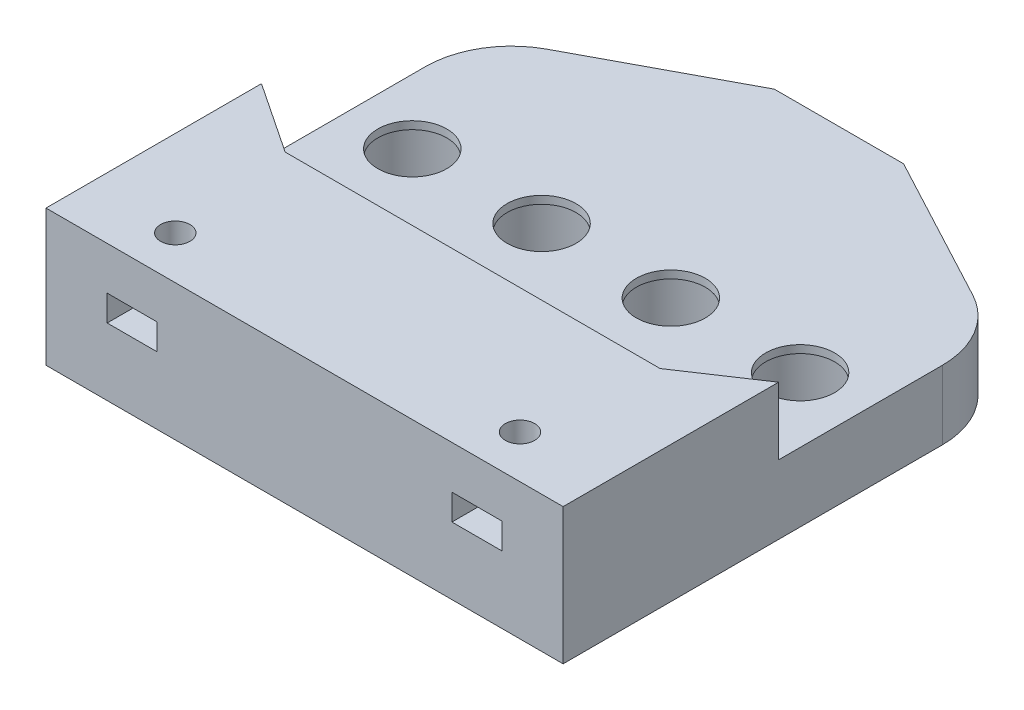
SolidWorks part; units mm, degrees
ref_plane "Front Plane" through (0, 0, 0) normal (0, 0, 1) x (1, 0, 0)
ref_plane "Top Plane" through (0, 0, 0) normal (0, 1, 0) x (1, 0, 0)
ref_plane "Right Plane" through (0, 0, 0) normal (1, 0, 0) x (0, 0, -1)
sketch "Sketch2" plane through (0, 0, 0) normal (0, 1, 0) x (1, 0, 0)
  line L0 (0, 0) -> (0, 35)
  line L1 (0, 35) -> (22.5, 47)
  line L2 (22.5, 47) -> (37.5, 47)
  line L3 (37.5, 47) -> (60, 35)
  line L4 (60, 35) -> (60, 0)
  line L5 (60, 0) -> (0, 0)
  line L6 (22.5, 20) -> (37.5, 20) construction
  line L7 (30, 47) -> (30, 0) construction
  circle A0 centre (7.5, 20) radius 4
  circle A1 centre (22.5, 20) radius 4
  circle A2 centre (37.5, 20) radius 4
  circle A3 centre (52.5, 20) radius 4
  point P17 (30, 20)
  dimension "D5" = 8
  dimension "D7" = 15
  dimension "D8" = 15
  dimension "D9" = 15
  dimension "D6" = 20
  dimension "D1" = 60
  dimension "D2" = 35
  dimension "D3" = 15
  dimension "D4" = 12
extrude "Boss-Extrude1" add sketch "Sketch2" along normal blind 8
sketch "Sketch3" plane through (0, 8, 0) normal (0, 1, 0) x (1, 0, 0)
  line L0 (0, 0) -> (0, 10)
  line L1 (0, 35) -> (0, 0) construction
  line L2 (0, 10) -> (15, 0)
  line L3 (0, 0) -> (60, 0) construction
  line L4 (15, 0) -> (0, 0)
  line L5 (60, 0) -> (60, 10)
  line L6 (60, 0) -> (60, 35) construction
  line L7 (60, 10) -> (45, 0)
  line L8 (45, 0) -> (60, 0)
  line L9 (51.75, 4.5) -> (8.25, 4.5)
  line M8 (0, 0) -> (60, 0)
  line M9 (60, 0) -> (60, 35)
  line M13 (0, 35) -> (0, 0)
  dimension "D1" = 15
  dimension "D2" = 10
  dimension "D3" = 4.5
extrude "Boss-Extrude2" add sketch "Sketch3" along normal blind 7.8 contours L2 M13 M8 | L7 L9 L2 M8 | L7 M9 M8 region at (5, 8, -3.3333) region at (30, 8, -2.3878) region at (55, 8, -3.3333)
sketch "Sketch5" plane through (0, 0, 0) normal (0, 1, 0) x (1, 0, 0)
  circle A0 centre (7.5, 20) radius 6.55
  circle A1 centre (22.5, 20) radius 6.55
  circle A2 centre (37.5, 20) radius 6.55
  circle A3 centre (52.5, 20) radius 6.55
  dimension "D1" = 13.1
extrude "Cut-Extrude2" cut sketch "Sketch5" along normal blind 7.1
fillet "Fillet1" radius 10 2 edges at (0, 4, -35) (60, 4, -35)
sketch "Sketch7" plane through (0, 0, 0) normal (0, 0, 1) x (1, 0, 0)
  line L1 (0, 15.8) -> (60, 15.8)
  line L2 (0, 15.8) -> (0, 0)
  line L3 (0, 0) -> (60, 0)
  line L4 (60, 15.8) -> (60, 0)
extrude "Boss-Extrude3" add sketch "Sketch7" along normal blind 15
sketch "Sketch8" plane through (0, 15.8, 0) normal (0, 1, 0) x (1, 0, 0)
  line L0 (60, -15) -> (0, -15) construction
  line L1 (0, 10) -> (0, -15) construction
  line L2 (30, 47) -> (30, -15) construction
  line L3 (37.5, 47) -> (22.5, 47) construction
  circle A0 centre (10, -10) radius 1.7
  circle A1 centre (50, -10) radius 1.7
  dimension "D1" = 3.4
  dimension "D2" = 5
  dimension "D3" = 10
extrude "Cut-Extrude3" cut sketch "Sketch8" against normal blind 10
sketch "Sketch9" plane through (0, 15.8, 0) normal (0, 1, 0) x (1, 0, 0)
  line L0 (30, -15) -> (30, 47) construction
  line L1 (52.9, -8.3257) -> (50, -6.6514)
  line L2 (50, -6.6514) -> (47.1, -8.3257)
  line L3 (47.1, -8.3257) -> (47.1, -11.6743)
  line L4 (47.1, -11.6743) -> (50, -13.3486)
  line L5 (50, -13.3486) -> (52.9, -11.6743)
  line L6 (52.9, -11.6743) -> (52.9, -8.3257)
  line L7 (60, -15) -> (0, -15) construction
  line L8 (37.5, 47) -> (22.5, 47) construction
  line L9 (52.9, -11.6743) -> (52.9, -15)
  line L10 (52.9, -15) -> (47.1, -15)
  line L11 (47.1, -15) -> (47.1, -11.6743)
  line L12 (12.9, -15) -> (12.9, -11.6743)
  line L13 (7.1, -15) -> (12.9, -15)
  line L14 (7.1, -11.6743) -> (7.1, -15)
  line L15 (7.1, -11.6743) -> (7.1, -8.3257)
  line L16 (10, -13.3486) -> (7.1, -11.6743)
  line L17 (12.9, -11.6743) -> (10, -13.3486)
  line L18 (12.9, -8.3257) -> (12.9, -11.6743)
  line L19 (10, -6.6514) -> (12.9, -8.3257)
  line L20 (7.1, -8.3257) -> (10, -6.6514)
  circle A0 centre (50, -10) radius 2.9 construction
  circle A1 centre (10, -10) radius 2.9 construction
  circle M8 centre (10, -10) radius 1.7
  circle M9 centre (50, -10) radius 1.7
  line M12 (0, -15) -> (60, -15)
  dimension "D1" = 5.8
extrude "Cut-Extrude4" cut sketch "Sketch9" against normal blind 3 from offset 5 contours L12 L17 L16 L14 M12 | M8 | L20 L15 L16 L17 L18 L19 M8 | L5 L6 L1 L2 L3 L4 M9 | M9 | L11 L9 L5 L4 M12 region at (52.8114, 15.8, 10) region at (10, 15.8, 13.7088) region at (50, 15.8, 13.7088) region at (11.4057, 15.8, 12.4347) region at (10, 15.8, 10) region at (50, 15.8, 10) offset against normal yes
sketch "Sketch10" plane through (0, 0, 0) normal (0, -1, 0) x (-1, 0, 0)
  line L0 (-37.5, 47) -> (-22.5, 47) construction
  line L1 (-35, 39) -> (-25, 39) construction
  circle A0 centre (-25, 39) radius 2.2
  circle A1 centre (-35, 39) radius 2.2
  circle A2 centre (-25, 1) radius 2.2
  circle A3 centre (-35, 1) radius 2.2
  point P8 (-30, 47)
  point P9 (-30, 39)
  dimension "D1" = 4.4
  dimension "D4" = 8
  dimension "D2" = 10
  dimension "D3" = 38
extrude "Cut-Extrude5" cut sketch "Sketch10" against normal blind 7
sketch "Sketch11" plane through (0, 0, 0) normal (0, -1, 0) x (-1, 0, 0)
  line L0 (0, -15) -> (-60, -15) construction
  line L1 (-30, 47) -> (-30, -15) construction
  line L2 (-37.5, 47) -> (-22.5, 47) construction
  circle A0 centre (-23, -10) radius 2.2
  circle A1 centre (-37, -10) radius 2.2
  dimension "D1" = 4.4
  dimension "D2" = 5
  dimension "D3" = 7
extrude "Cut-Extrude6" cut sketch "Sketch11" against normal blind 8
